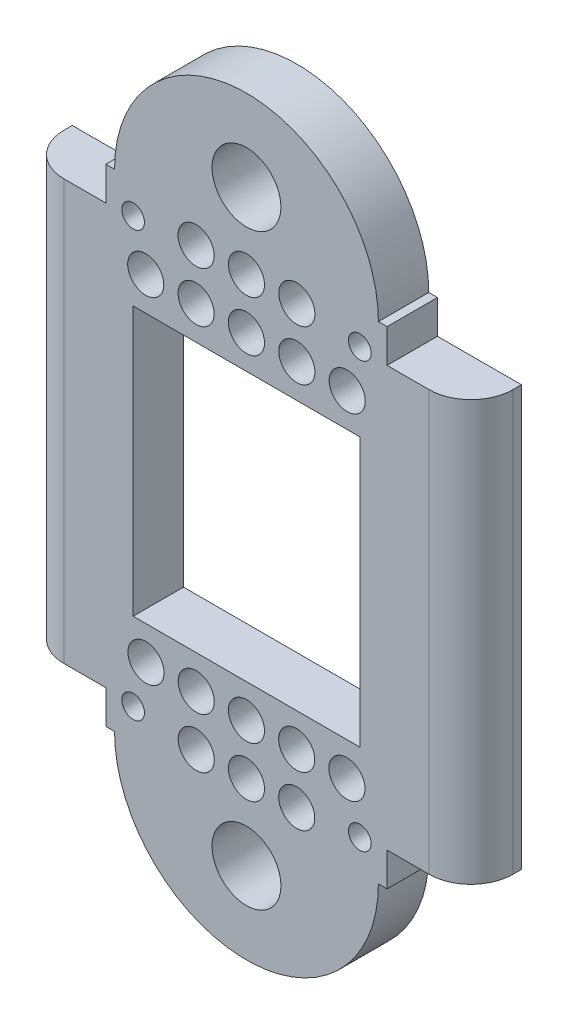
SolidWorks part; units mm, degrees
ref_plane "Front Plane" through (0, 0, 0) normal (0, 0, 1) x (1, 0, 0)
ref_plane "Top Plane" through (0, 0, 0) normal (0, 1, 0) x (1, 0, 0)
ref_plane "Right Plane" through (0, 0, 0) normal (1, 0, 0) x (0, 0, -1)
sketch "Sketch1" plane through (0, 0, 0) normal (0, 0, 1) x (1, 0, 0)
  line L0 (-13.5, -16) -> (13.5, -16)
  line L1 (-16.75, 29) -> (-15.7154, 29)
  line L2 (-16.75, 29) -> (-16.75, 25)
  line L3 (-16.75, -29) -> (-15.7154, -29)
  line L4 (16.75, 29) -> (16.75, 25)
  line L5 (-13.5, 16) -> (13.5, 16)
  line L6 (-13.5, 16) -> (-13.5, -16)
  line L8 (13.5, 16) -> (13.5, -16)
  line L9 (26.75, 25) -> (26.75, -25)
  line L10 (0, 0) -> (0, 6.7852) construction
  line L11 (26.75, 25) -> (16.75, 25)
  line L13 (26.75, -25) -> (16.75, -25)
  line L14 (-19.5, 29.3) -> (19.5, 29.3) construction
  line L15 (-19.5, 29.3) -> (-19.5, -29.3) construction
  line L16 (-19.5, -29.3) -> (19.5, -29.3) construction
  line L17 (19.5, 29.3) -> (19.5, -29.3) construction
  line L18 (-26.75, -25) -> (-16.75, -25)
  line L19 (-26.75, 25) -> (-16.75, 25)
  line L20 (0, 0) -> (4.3335, 0) construction
  line L21 (15.7154, 29) -> (16.75, 29)
  line L22 (15.7154, -29) -> (16.75, -29)
  line L23 (-26.75, 25) -> (-26.75, -25)
  line L24 (-16.75, -25) -> (-16.75, -29)
  line L25 (16.75, -25) -> (16.75, -29)
  circle A2 centre (-13.5, 25.3) radius 1.35
  circle A4 centre (13.5, -25.3) radius 1.35
  circle A5 centre (-13.5, -25.3) radius 1.35
  circle A6 centre (13.5, 25.3) radius 1.35
  circle A8 centre (0, 35) radius 4.1
  circle A13 centre (0, -35) radius 4.1
  arc A16 (-15.7154, 29) -> (15.7154, 29) centre (0, 29) cw
  arc A17 (-15.7154, -29) -> (15.7154, -29) centre (0, -29) ccw
  point P11 (0, 16)
  point P12 (-13.5, 0)
  point P29 (19.5, 0)
  point P30 (0, 29.3)
  dimension "D8" = 2.7
  dimension "D22" = 8.2
  dimension "D23" = 6
  dimension "D1" = 27
  dimension "D2" = 33.5
  dimension "D3" = 58
  dimension "D4" = 32
  dimension "D5" = 4
  dimension "D6" = 4
  dimension "D7" = 10
  dimension "D9" = 58.6
  dimension "D10" = 39
  dimension "D11" = 6
  dimension "D12" = 4
  dimension "D13" = 4
  dimension "D14" = 6
  dimension "D15" = 6
  dimension "D16" = 6
  dimension "D17" = 4
  dimension "D18" = 4
extrude "Boss-Extrude1" add sketch "Sketch1" along normal blind 6
sketch "Sketch2" plane through (0, 0, 6) normal (0, 0, 1) x (1, 0, 0)
  line L3 (13.5, 16) -> (-13.5, 16) construction
  line L4 (-13.5, -16) -> (13.5, -16) construction
  circle A0 centre (-12, 20) radius 2.15
  circle A1 centre (-6, 20) radius 2.15
  circle A2 centre (0, 20) radius 2.15
  circle A3 centre (6, 20) radius 2.15
  circle A4 centre (12, 20) radius 2.15
  circle A5 centre (-6, 26) radius 2.15
  circle A6 centre (0, 26) radius 2.15
  circle A7 centre (6, 26) radius 2.15
  circle A8 centre (-11.9673, -20) radius 2.15
  circle A9 centre (-5.9837, -20) radius 2.15
  circle A10 centre (0, -20) radius 2.15
  circle A11 centre (5.9837, -20) radius 2.15
  circle A12 centre (11.9673, -20) radius 2.15
  circle A13 centre (-5.9837, -26) radius 2.15
  circle A14 centre (0, -26) radius 2.15
  circle A15 centre (5.9837, -26) radius 2.15
  dimension "D1" = 4.3
  dimension "D5" = 4.3
  dimension "D11" = 4.3
  dimension "D12" = 4.3
  dimension "D13" = 4.3
  dimension "D14" = 4.3
  dimension "D15" = 4.3
  dimension "D16" = 4.3
  dimension "D2" = 4
  dimension "D3" = 4
  dimension "D6" = 6
  dimension "D10" = 6
  dimension "D4" = 5
  dimension "D9" = 5
extrude "Cut-Extrude1" cut sketch "Sketch2" against normal blind 4.2
fillet "Fillet1" radius 5 1 edges at (-26.75, 0, 6)
fillet "Fillet2" radius 5 1 edges at (26.75, 0, 6)
